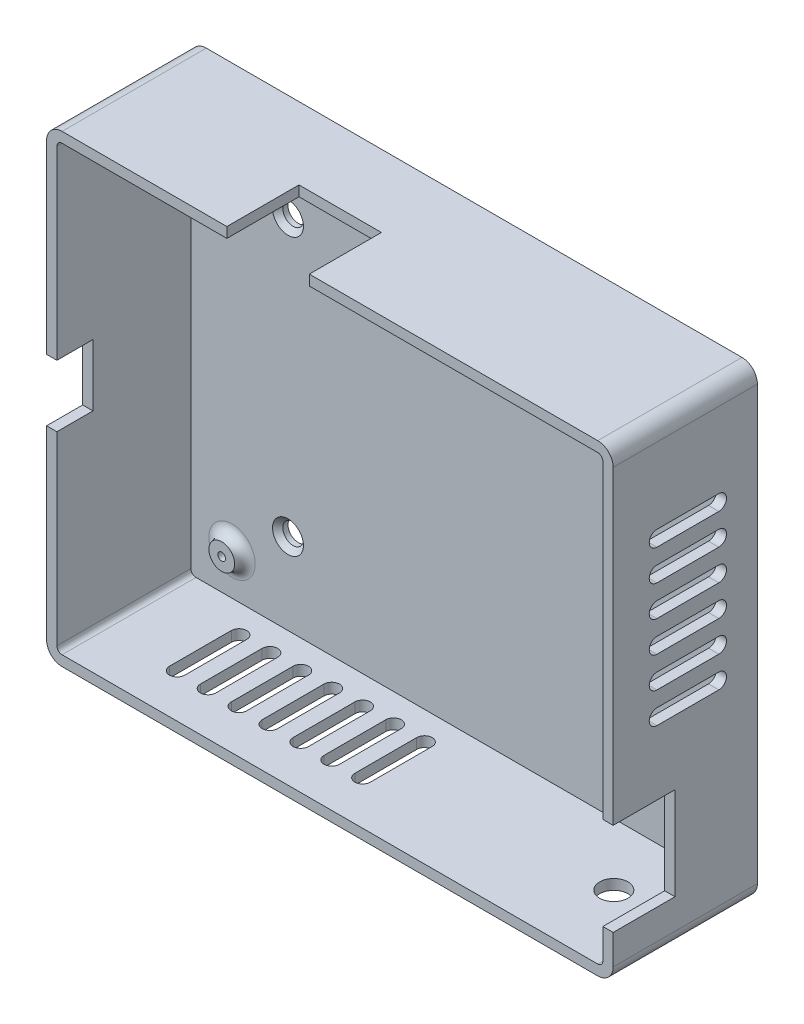
SolidWorks part; units mm, degrees
ref_plane "Front Plane" through (0, 0, 0) normal (0, 0, 1) x (1, 0, 0)
ref_plane "Top Plane" through (0, 0, 0) normal (0, 1, 0) x (1, 0, 0)
ref_plane "Right Plane" through (0, 0, 0) normal (1, 0, 0) x (0, 0, -1)
sketch "Sketch2" plane through (0, 0, 0) normal (0, 0, 1) x (1, 0, 0)
  line L1 (-52, -45) -> (52, -45)
  line L2 (-55, -42) -> (-55, 42)
  line L3 (-52, 45) -> (52, 45)
  line L4 (55, -42) -> (55, 42)
  line L5 (-55, -45) -> (55, 45) construction
  line L6 (-55, 45) -> (55, -45) construction
  arc A0 (52, -45) -> (55, -42) centre (52, -42) ccw
  arc A1 (-52, -45) -> (-55, -42) centre (-52, -42) cw
  arc A2 (-55, 42) -> (-52, 45) centre (-52, 42) cw
  arc A3 (52, 45) -> (55, 42) centre (52, 42) cw
  point P0 (0, 0)
  dimension "D3" = 3
  dimension "D1" = 90
  dimension "D2" = 110
extrude "Boss-Extrude1" add sketch "Sketch2" along normal blind 2
sketch "Sketch3" plane through (0, 0, 2) normal (0, 0, 1) x (1, 0, 0)
  line L0 (52, 43) -> (-52, 43)
  line L1 (-53, 42) -> (-53, -42)
  line L2 (-52, -43) -> (52, -43)
  line L3 (53, -42) -> (53, 42)
  line L4 (55, -42) -> (55, 42)
  line L5 (52, 45) -> (-52, 45)
  line L6 (-55, 42) -> (-55, -42)
  line L7 (-52, -45) -> (52, -45)
  line L8 (55, -42) -> (55, 42)
  line L9 (52, 45) -> (-52, 45)
  line L10 (-55, 42) -> (-55, -42)
  line L11 (-52, -45) -> (52, -45)
  arc A0 (-52, 43) -> (-53, 42) centre (-52, 42) ccw
  arc A1 (-53, -42) -> (-52, -43) centre (-52, -42) ccw
  arc A2 (52, -43) -> (53, -42) centre (52, -42) ccw
  arc A3 (53, 42) -> (52, 43) centre (52, 42) ccw
  arc A4 (52, -45) -> (55, -42) centre (52, -42) ccw
  arc A5 (55, 42) -> (52, 45) centre (52, 42) ccw
  arc A6 (-52, 45) -> (-55, 42) centre (-52, 42) ccw
  arc A7 (-55, -42) -> (-52, -45) centre (-52, -42) ccw
  arc A8 (52, -45) -> (55, -42) centre (52, -42) ccw
  arc A9 (55, 42) -> (52, 45) centre (52, 42) ccw
  arc A10 (-52, 45) -> (-55, 42) centre (-52, 42) ccw
  arc A11 (-55, -42) -> (-52, -45) centre (-52, -42) ccw
  dimension "D1" = 0
  dimension "D2" = 2
extrude "Boss-Extrude2" add sketch "Sketch3" along normal blind 26
sketch "Sketch5" plane through (0, 0, 0) normal (0, 0, -1) x (-1, 0, 0)
  line L1 (-45, -35) -> (45, -35) construction
  line L2 (-45, -35) -> (-45, 35) construction
  line L3 (-45, 35) -> (45, 35) construction
  line L4 (45, -35) -> (45, 35) construction
  line L5 (-45, -35) -> (45, 35) construction
  line L6 (-45, 35) -> (45, -35) construction
  circle A0 centre (45, 35) radius 0.75
  circle A1 centre (-45, 35) radius 0.75
  circle A2 centre (-45, -35) radius 0.75
  circle A3 centre (45, -35) radius 0.75
  circle A4 centre (45, 35) radius 2.5
  circle A5 centre (-45, 35) radius 2.5
  circle A6 centre (-45, -35) radius 2.5
  circle A7 centre (45, -35) radius 2.5
  point P0 (0, 0)
  dimension "D1" = 1.5
  dimension "D2" = 70
  dimension "D4" = 5
  dimension "D3" = 90
extrude "Boss-Extrude4" add sketch "Sketch5" against normal blind 4
fillet "Fillet2" radius 2 4 edges at (-42.5, -35, 2) (47.5, -35, 2) (47.5, 35, 2) (-42.5, 35, 2)
sketch "Sketch8" plane through (0, 0, 2) normal (0, 0, 1) x (1, 0, 0)
  line L0 (45, -35) -> (45, 35) construction
  line L1 (45, 35) -> (45, 43) construction
  line L2 (52, 43) -> (-52, 43) construction
sketch "Sketch9" plane through (0, 43, 0) normal (0, -1, 0) x (-1, 0, 0)
  line L0 (-45, -2) -> (-45, -28) construction
  line L1 (-52, -28) -> (52, -28) construction
  line L2 (12, -2) -> (12, -28) construction
  line L3 (-52, -2) -> (52, -2) construction
  line L5 (20, -14) -> (4, -14)
  line L6 (20, -14) -> (20, -28)
  line L7 (20, -28) -> (4, -28)
  line L8 (4, -14) -> (4, -28)
  line L9 (20, -14) -> (4, -28) construction
  line L10 (20, -28) -> (4, -14) construction
  point P9 (12, -21)
  dimension "D1" = 57
  dimension "D2" = 12
  dimension "D3" = 16
extrude "Cut-Extrude3" cut sketch "Sketch9" against normal blind 2.5
sketch "Sketch11" plane through (0, -45, 0) normal (0, -1, 0) x (-1, 0, 0)
  line L0 (-52, -14) -> (52, -14) construction
  line L1 (-52, -28) -> (-52, 0) construction
  line L2 (52, -28) -> (52, 0) construction
  circle A0 centre (-41.1265, -14) radius 2.75
extrude "Cut-Extrude5" cut sketch "Sketch11" against normal blind 2.5
sketch "Sketch12" plane through (-55, 0, 0) normal (-1, 0, 0) x (0, 0, 1)
  line L0 (28, 42) -> (28, -42) construction
  line L1 (28, 6) -> (21, 6)
  line L2 (28, 6) -> (28, -6)
  line L3 (28, -6) -> (21, -6)
  line L4 (21, 6) -> (21, -6)
  line L5 (0, 0) -> (28, 0) construction
  line L6 (0, 42) -> (0, -42) construction
  line L7 (28, 6) -> (21, -6) construction
  line L8 (28, -6) -> (21, 6) construction
  point P10 (24.5, 0)
  dimension "D1" = 7
  dimension "D2" = 12
extrude "Cut-Extrude6" cut sketch "Sketch12" against normal up to next
sketch "Sketch13" plane through (55, 0, 0) normal (1, 0, 0) x (0, 0, -1)
  line L0 (-28, -42) -> (-28, 42) construction
  line L1 (-28, -36.1902) -> (-16, -36.1902)
  line L2 (-28, -36.1902) -> (-28, -18.1902)
  line L3 (-28, -18.1902) -> (-16, -18.1902)
  line L4 (-16, -36.1902) -> (-16, -18.1902)
  dimension "D1" = 12
  dimension "D2" = 18
extrude "Cut-Extrude7" cut sketch "Sketch13" against normal blind 10
sketch "Sketch14" plane through (0, 0, 2) normal (0, 0, 1) x (1, 0, 0)
  line L0 (-45, -35.75) -> (45, 35) construction
  line L1 (0, -0.375) -> (-10.5005, 12.9825) construction
  line L2 (0, -0.375) -> (-47.0216, -0.375) construction
  circle A0 centre (-45, -35) radius 0.75 construction
  circle A1 centre (-34.1369, -27.2104) radius 2
  circle A2 centre (34.1369, 26.4604) radius 2
  circle A3 centre (34.1369, -27.2104) radius 2
  circle A4 centre (-34.1369, 26.4604) radius 2
  dimension "D1" = 4
extrude "Cut-Extrude8" cut sketch "Sketch14" against normal blind 10
chamfer "Chamfer1" distance 1 4 edges at (32.1369, 26.4604, 2) (-32.1369, -27.2104, 2) (36.1369, -27.2104, 2) (-36.1369, 26.4604, 2)
sketch "Sketch16" plane through (0, -45, 0) normal (0, -1, 0) x (-1, 0, 0)
  line L0 (38.1471, -19.5) -> (38.1471, -7.5) construction
  line L1 (36.6471, -19.5) -> (36.6471, -7.5)
  line L2 (39.6471, -19.5) -> (39.6471, -7.5)
  line L3 (38.1471, -7.5) -> (4.6045, -7.5) construction
  line L4 (32.1471, -7.5) -> (-1.3955, -7.5) construction
  line L5 (32.1471, -19.5) -> (32.1471, -7.5) construction
  line L6 (30.6471, -19.5) -> (30.6471, -7.5)
  line L7 (33.6471, -19.5) -> (33.6471, -7.5)
  line L8 (26.1471, -7.5) -> (-7.3955, -7.5) construction
  line L9 (26.1471, -19.5) -> (26.1471, -7.5) construction
  line L10 (24.6471, -19.5) -> (24.6471, -7.5)
  line L11 (27.6471, -19.5) -> (27.6471, -7.5)
  line L12 (20.1471, -7.5) -> (-13.3955, -7.5) construction
  line L13 (20.1471, -19.5) -> (20.1471, -7.5) construction
  line L14 (18.6471, -19.5) -> (18.6471, -7.5)
  line L15 (21.6471, -19.5) -> (21.6471, -7.5)
  line L16 (14.1471, -7.5) -> (-19.3955, -7.5) construction
  line L17 (14.1471, -19.5) -> (14.1471, -7.5) construction
  line L18 (12.6471, -19.5) -> (12.6471, -7.5)
  line L19 (15.6471, -19.5) -> (15.6471, -7.5)
  line L20 (8.1471, -7.5) -> (-25.3955, -7.5) construction
  line L21 (8.1471, -19.5) -> (8.1471, -7.5) construction
  line L22 (6.6471, -19.5) -> (6.6471, -7.5)
  line L23 (9.6471, -19.5) -> (9.6471, -7.5)
  line L24 (2.1471, -7.5) -> (-31.3955, -7.5) construction
  line L25 (2.1471, -19.5) -> (2.1471, -7.5) construction
  line L26 (0.6471, -19.5) -> (0.6471, -7.5)
  line L27 (3.6471, -19.5) -> (3.6471, -7.5)
  line L28 (52, 0) -> (-52, 0) construction
  arc A0 (36.6471, -19.5) -> (39.6471, -19.5) centre (38.1471, -19.5) ccw
  arc A1 (39.6471, -7.5) -> (36.6471, -7.5) centre (38.1471, -7.5) ccw
  arc A2 (30.6471, -19.5) -> (33.6471, -19.5) centre (32.1471, -19.5) ccw
  arc A3 (33.6471, -7.5) -> (30.6471, -7.5) centre (32.1471, -7.5) ccw
  arc A4 (24.6471, -19.5) -> (27.6471, -19.5) centre (26.1471, -19.5) ccw
  arc A5 (27.6471, -7.5) -> (24.6471, -7.5) centre (26.1471, -7.5) ccw
  arc A6 (18.6471, -19.5) -> (21.6471, -19.5) centre (20.1471, -19.5) ccw
  arc A7 (21.6471, -7.5) -> (18.6471, -7.5) centre (20.1471, -7.5) ccw
  arc A8 (12.6471, -19.5) -> (15.6471, -19.5) centre (14.1471, -19.5) ccw
  arc A9 (15.6471, -7.5) -> (12.6471, -7.5) centre (14.1471, -7.5) ccw
  arc A10 (6.6471, -19.5) -> (9.6471, -19.5) centre (8.1471, -19.5) ccw
  arc A11 (9.6471, -7.5) -> (6.6471, -7.5) centre (8.1471, -7.5) ccw
  arc A12 (0.6471, -19.5) -> (3.6471, -19.5) centre (2.1471, -19.5) ccw
  arc A13 (3.6471, -7.5) -> (0.6471, -7.5) centre (2.1471, -7.5) ccw
  point P2 (38.1471, -13.5)
  point P13 (32.1471, -13.5)
  point P22 (26.1471, -13.5)
  point P31 (20.1471, -13.5)
  point P40 (14.1471, -13.5)
  point P49 (8.1471, -13.5)
  point P58 (2.1471, -13.5)
  dimension "D3" = 1.5
  dimension "D4" = 7.5
  dimension "D1" = 7
  dimension "D2" = 12
extrude "Cut-Extrude9" cut sketch "Sketch16" against normal blind 10
sketch "Sketch17" plane through (55, 0, 0) normal (1, 0, 0) x (0, 0, -1)
  line L0 (-19.5, -4.1618) -> (-7.5, -4.1618) construction
  line L1 (-19.5, -2.6618) -> (-7.5, -2.6618)
  line L2 (-19.5, -5.6618) -> (-7.5, -5.6618)
  line L3 (0, -42) -> (0, 42) construction
  line L4 (-19.5, 1.8382) -> (-7.5, 1.8382) construction
  line L5 (-19.5, 3.3382) -> (-7.5, 3.3382)
  line L6 (-19.5, 0.3382) -> (-7.5, 0.3382)
  line L7 (-19.5, 7.8382) -> (-7.5, 7.8382) construction
  line L8 (-19.5, 9.3382) -> (-7.5, 9.3382)
  line L9 (-19.5, 6.3382) -> (-7.5, 6.3382)
  line L10 (-19.5, 13.8382) -> (-7.5, 13.8382) construction
  line L11 (-19.5, 15.3382) -> (-7.5, 15.3382)
  line L12 (-19.5, 12.3382) -> (-7.5, 12.3382)
  line L13 (-19.5, 19.8382) -> (-7.5, 19.8382) construction
  line L14 (-19.5, 21.3382) -> (-7.5, 21.3382)
  line L15 (-19.5, 18.3382) -> (-7.5, 18.3382)
  line L16 (-19.5, 25.8382) -> (-7.5, 25.8382) construction
  line L17 (-19.5, 27.3382) -> (-7.5, 27.3382)
  line L18 (-19.5, 24.3382) -> (-7.5, 24.3382)
  arc A0 (-19.5, -2.6618) -> (-19.5, -5.6618) centre (-19.5, -4.1618) ccw
  arc A1 (-7.5, -5.6618) -> (-7.5, -2.6618) centre (-7.5, -4.1618) ccw
  arc A2 (-19.5, 3.3382) -> (-19.5, 0.3382) centre (-19.5, 1.8382) ccw
  arc A3 (-7.5, 0.3382) -> (-7.5, 3.3382) centre (-7.5, 1.8382) ccw
  arc A4 (-19.5, 9.3382) -> (-19.5, 6.3382) centre (-19.5, 7.8382) ccw
  arc A5 (-7.5, 6.3382) -> (-7.5, 9.3382) centre (-7.5, 7.8382) ccw
  arc A6 (-19.5, 15.3382) -> (-19.5, 12.3382) centre (-19.5, 13.8382) ccw
  arc A7 (-7.5, 12.3382) -> (-7.5, 15.3382) centre (-7.5, 13.8382) ccw
  arc A8 (-19.5, 21.3382) -> (-19.5, 18.3382) centre (-19.5, 19.8382) ccw
  arc A9 (-7.5, 18.3382) -> (-7.5, 21.3382) centre (-7.5, 19.8382) ccw
  arc A10 (-19.5, 27.3382) -> (-19.5, 24.3382) centre (-19.5, 25.8382) ccw
  arc A11 (-7.5, 24.3382) -> (-7.5, 27.3382) centre (-7.5, 25.8382) ccw
  point P2 (-13.5, -4.1618)
  point P13 (-13.5, 1.8382)
  point P20 (-13.5, 7.8382)
  point P27 (-13.5, 13.8382)
  point P34 (-13.5, 19.8382)
  point P41 (-13.5, 25.8382)
  dimension "D2" = 1.5
  dimension "D3" = 7.5
  dimension "D1" = 12
  dimension "D4" = 6
extrude "Cut-Extrude10" cut sketch "Sketch17" against normal blind 10
